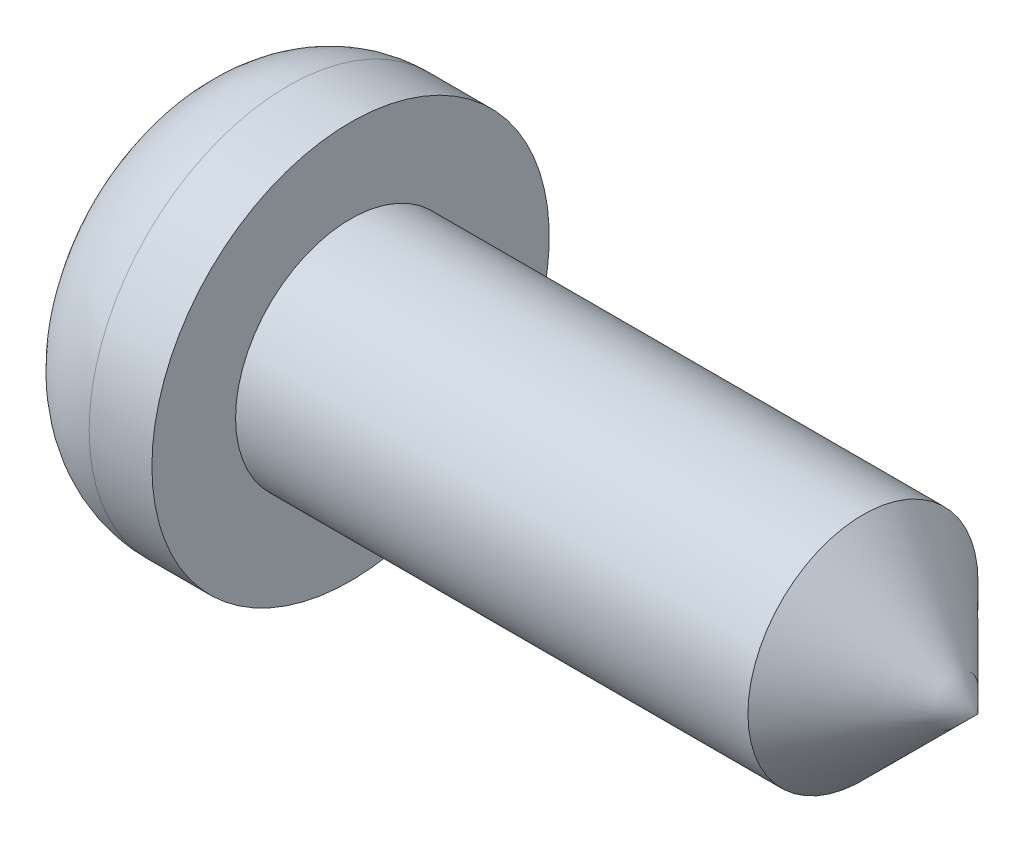
SolidWorks part; units mm, degrees
ref_plane "前视基准面" through (0, 0, 0) normal (0, 0, 1) x (1, 0, 0)
ref_plane "上视基准面" through (0, 0, 0) normal (0, 1, 0) x (1, 0, 0)
ref_plane "右视基准面" through (0, 0, 0) normal (1, 0, 0) x (0, 0, -1)
sketch "草图1" plane through (0, 0, 0) normal (0, 0, 1) x (1, 0, 0)
  line L0 (-6.9765, 0) -> (9.0335, 0) construction
  line L1 (0, 0) -> (0, 1.9)
  line L2 (7.6, 0) -> (6.5, 1.1)
  line L3 (1.6, 1.1) -> (6.5, 1.1)
  line L5 (0, 0) -> (7.6, 0)
  line L8 (0, 1.9) -> (1.6, 1.9)
  line L9 (1.6, 1.9) -> (1.6, 1.1)
  dimension "D1" = 1.1
  dimension "D2" = 1.9
  dimension "D3" = 1.6
  dimension "D4" = 0
  dimension "D5" = 6
  dimension "D6" = 45
revolve "旋转1" add sketch "草图1" angle 360 about L0
cosmetic thread "装饰螺纹线1" parameters "D1"=12.75, "D2"=2.013
sketch "草图2" plane through (0, 0, 0) normal (-1, 0, 0) x (0, 0, 1)
  line L0 (-1, 0) -> (1.4943, 0) construction
  line L1 (0, 1.2902) -> (0, -1.1678) construction
  line L2 (-0.3, 0.3) -> (-1, 0.3)
  line L3 (-1, 0.3) -> (-1, -0.3)
  line L4 (-1, -0.3) -> (-0.3, -0.3)
  line L5 (-0.3, -0.3) -> (-0.3, -1)
  line L6 (-0.3, -1) -> (0.3, -1)
  line L7 (0.3, -1) -> (0.3, -0.3)
  line L8 (0.3, -0.3) -> (1, -0.3)
  line L9 (1, -0.3) -> (1, 0.3)
  line L10 (1, 0.3) -> (0.3, 0.3)
  line L11 (0.3, 0.3) -> (0.3, 1)
  line L12 (0.3, 1) -> (-0.3, 1)
  line L13 (-0.3, 1) -> (-0.3, 0.3)
  dimension "D1" = 0.3
  dimension "D2" = 0.3
  dimension "D3" = 1
  dimension "D4" = 0.3
  dimension "D5" = 0.3
  dimension "D6" = 1
  dimension "D7" = 0.3
  dimension "D8" = 0.3
  dimension "D9" = 1
  dimension "D10" = 1
  dimension "D11" = 0.3
  dimension "D12" = 0.3
extrude "切除-拉伸1" cut sketch "草图2" against normal blind 0.5
fillet "圆角1" radius 1 1 edges at (0, 0, 1.9)
